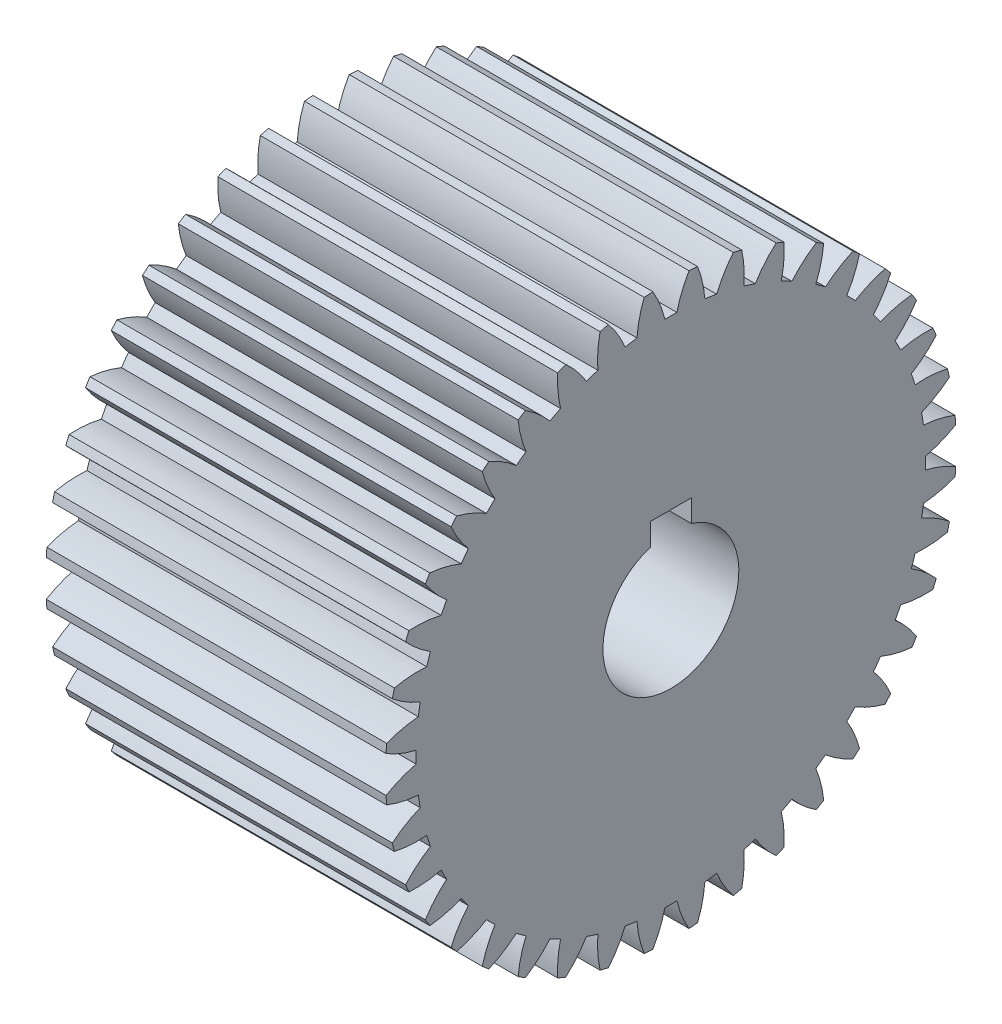
SolidWorks part; units mm, degrees
ref_plane "Plane1" through (0, 0, 0) normal (0, 0, 1) x (1, 0, 0)
ref_plane "Plane2" through (0, 0, 0) normal (0, 1, 0) x (1, 0, 0)
ref_plane "Plane3" through (0, 0, 0) normal (1, 0, 0) x (0, 0, -1)
sketch "HoldingSke" plane through (0, 0, 0) normal (0, 1, 0) x (1, 0, 0)
  line L0 (0, 0) -> (0.383, -0.3214)
  line L1 (-15, 0) -> (100, 0) construction
  line L2 (0, 0) -> (-2.1039, 2.3779)
  line L3 (0, 0) -> (-11.863, 4.5341)
  line L4 (0, 0) -> (6.6156, 5.5511)
  line L5 (0, 0) -> (-46.8476, -17.4728)
  line L6 (0, 0) -> (-41.4481, -27.9652)
  line L7 (-2.1039, 2.3779) -> (8.6586, 51.2059)
  line L8 (-76.2, 54.61) -> (-73.4, 54.61)
  line L9 (-71.009, 38.7566) -> (-53.1078, 45.2721)
  line L10 (-76.2, 71.12) -> (104.1128, 71.12)
  line L11 (0, 0) -> (-50, 0)
  line L12 (-76.2, 101.6) -> (-76.133, 101.6)
  line L13 (24.9733, 27.94) -> (52.9518, 28.4284)
  line L14 (24.9733, 27.94) -> (24.9743, 27.94)
  line L15 (24.9733, 27.94) -> (100.4006, 29.5858)
  line L16 (-63.627, -2) -> (-12.827, -2)
  circle A0 centre (0, 0) radius 10
  circle A1 centre (0, 0) radius 37.499
  circle A2 centre (0, 0) radius 37.5
  circle A3 centre (0, 0) radius 10
  dimension "Num_teeth" = 40
  dimension "Pitch_radius" = 180.3128
  dimension "Width" = 50
  dimension "Thickness" = 50
sketch "BasProSke" plane through (0, 0, 0) normal (0, 1, 0) x (1, 0, 0)
  line L0 (-10, 0) -> (60, 0) construction
  line L1 (0, 0) -> (0, 42)
  line L2 (0, 0) -> (50, 0)
  line L3 (50, 0) -> (50, 42)
  line L4 (50, 42) -> (0, 42)
  dimension "Thickness" = 50
  dimension "Diameter" = 84
revolve "Base-Revolve" add sketch "BasProSke" angle 360 about L0
sketch "TooCutSke" plane through (0, 0, 0) normal (1, 0, 0) x (0, 0, -1)
  line L1 (0, 0) -> (0, 107) construction
  line L2 (0, 0) -> (-1.6876, 39.9644) construction
  line L3 (0, 0) -> (-6.2726, 79.7007) construction
  line L4 (-1.6876, 39.9644) -> (-3.1363, 39.8504) construction
  arc A0 (0.8828, 37.4886) -> (-0.8828, 37.4886) centre (0, 0) ccw
  arc A1 (2.6784, 41.94) -> (-2.6784, 41.94) centre (0, 0) ccw
  circle A2 centre (0, 0) radius 40 construction
  circle A3 centre (0, 0) radius 37.5877 construction
  arc A4 (-0.8828, 37.4886) -> (-2.6784, 41.94) centre (-16.451, 33.7965) ccw
  arc A5 (2.6784, 41.94) -> (0.8828, 37.4886) centre (16.451, 33.7965) ccw
extrude "ToothCut" cut sketch "TooCutSke" along normal through all
fillet "Breaks" [suppressed] radius 0.04 tangent propagation no
fillet "RootFillets" [suppressed] radius 0.501
pattern_circular "TeethCuts" count 40 every 9 about axis through (-10, 0, 0) along (1, 0, 0) of "ToothCut", "RootFillets", "Breaks"
sketch "HubNeaOneSke" plane through (0, 0, 0) normal (-1, 0, 0) x (0, 0, 1)
  circle A0 centre (0, 0) radius 37.499
  dimension "Diameter" = 74.998
extrude "HubNearOne" [suppressed] add sketch "HubNeaOneSke" along normal blind 34.0001
sketch "HubNeaBotSke" plane through (0, 0, 0) normal (-1, 0, 0) x (0, 0, 1)
  circle A0 centre (0, 0) radius 37.499
  dimension "Diameter" = 74.998
extrude "HubNearBoth" [suppressed] add sketch "HubNeaBotSke" along normal blind 17
ref_plane "FarPln" through (50, 0, 0) normal (1, 0, 0) x (0, 0, -1)
sketch "HubFarSke" plane through (50, 0, 0) normal (1, 0, 0) x (0, 0, -1)
  circle A0 centre (0, 0) radius 37.499
  dimension "Diameter" = 74.998
extrude "HubFar" [suppressed] add sketch "HubFarSke" along normal blind 17
sketch "BorSke" plane through (0, 0, 0) normal (1, 0, 0) x (0, 0, -1)
  circle A0 centre (0, 0) radius 10
  dimension "Diameter" = 20
extrude "Bore" cut sketch "BorSke" along normal mid plane 100.0001
sketch "KeySke" plane through (0, 0, 0) normal (1, 0, 0) x (0, 0, -1)
  line L0 (-3, 0) -> (-3, 12.8)
  line L1 (-3, 12.8) -> (3, 12.8)
  line L2 (3, 12.8) -> (3, 0)
  line L3 (0, 0) -> (0, 34) construction
  line L4 (-3, 0) -> (3, 0)
  dimension "Width" = 6
extrude "Keyway" cut sketch "KeySke" along normal mid plane 100.0001
pattern_circular "Keyway2" [suppressed] count 2 every 90 about axis through (-10, 0, 0) along (1, 0, 0) reverse direction yes
equation "' \"Module@HoldingSke\" = 6.35"
equation "' \"Num_teeth@HoldingSke\" = 12"
equation "' \"Ap@HoldingSke\" =  20"
equation "' \"Ap@HoldingSke\" = 20"
equation "' \"Width@HoldingSke\" = 0.5 * 25.4"
equation "' \"Hub_dia@HoldingSke\"= 1 * 25.4"
equation "' \"Hub_dia@HoldingSke\" = 1 * 25.4"
equation "' \"Overall_len@HoldingSke\" = 1.0 * 25.4"
equation "' \"Bore@HoldingSke\" = 0.75 * 25.4"
equation "' \"T_dim@HoldingSke\" = 0.1 * 25.4"
equation "' \"Width@KeySke\" = 0.25 * 25.4"
equation "' \"Show_teeth@HoldingSke\" = 13"
equation "' \"Backlash@HoldingSke\" = 0.009 * 25.4"
equation "' \"Addendum_fac@HoldingSke\" = 1.0"
equation "' \"Dedendum_fac@HoldingSke\" = 1.25"
equation "' \"Dedendum_add@HoldingSke\" = 0.00005 * 25.4"
equation "' \"Clearance_fac@HoldingSke\" = 0.25"
equation "\"Pitch@HoldingSke\" = 1 / \"Module@HoldingSke\""
equation "\"Overcut_dia@TooCutSke\" = (\"Num_teeth@HoldingSke\" + 2 * \"Addendum_fac@HoldingSke\") / \"Pitch@HoldingSke\" + 0.002 * 25.4"
equation "\"Pitch_dia@TooCutSke\" = \"Num_teeth@HoldingSke\" / \"Pitch@HoldingSke\""
equation "\"Base_dia@TooCutSke\" = \"Num_teeth@HoldingSke\" / \"Pitch@HoldingSke\" * cos((\"Ap@HoldingSke\"  * 3.14159265 / 180))"
equation "\"Root_dia@TooCutSke\" = (\"Num_teeth@HoldingSke\" + 2) / \"Pitch@HoldingSke\" - 2 * (\"Addendum_fac@HoldingSke\" + \"Dedendum_fac@HoldingSke\") / \"Pitch@HoldingSke\" - \"Dedendum_add@HoldingSke\" * 2"
equation "\"Half_ang@TooCutSke\" = 180 / \"Num_teeth@HoldingSke\""
equation "\"Half_CT@TooCutSke\" = \"Num_teeth@HoldingSke\" / \"Pitch@HoldingSke\" * sin((3.14159265 / 2 / \"Num_teeth@HoldingSke\")) / 2 - 7 * \"Backlash@HoldingSke\" / 4"
equation "\"Flank_rad@TooCutSke\" = \"Num_teeth@HoldingSke\" / \"Pitch@HoldingSke\" / 5"
equation "\"Radius@RootFillets\" = \"Clearance_fac@HoldingSke\" / \"Pitch@HoldingSke\" + \"Dedendum_add@HoldingSke\""
equation "\"Break_rad@Breaks\" = 0.02 / \"Pitch@HoldingSke\""
equation "\"Thickness@HoldingSke\" = \"Width@HoldingSke\""
equation "\"OAL@HoldingSke\" = \"Thickness@HoldingSke\""
equation "\"MHD@HoldingSke\" = (\"Num_teeth@HoldingSke\" + 2) / \"Pitch@HoldingSke\" - 2 * (\"Addendum_fac@HoldingSke\" + \"Dedendum_fac@HoldingSke\")  / \"Pitch@HoldingSke\" - \"Dedendum_add@HoldingSke\" * 2"
equation "\"MBD@HoldingSke\" = (\"Num_teeth@HoldingSke\" + 2) / \"Pitch@HoldingSke\" - 2 * (\"Addendum_fac@HoldingSke\" + \"Dedendum_fac@HoldingSke\")  / \"Pitch@HoldingSke\" - \"Dedendum_add@HoldingSke\" * 2 - 0.002 * 25.4"
equation "\"MHD@HoldingSke\" = ((sgn( \"MHD@HoldingSke\" - \"Hub_dia@HoldingSke\" )-1)*( \"MHD@HoldingSke\" - \"Hub_dia@HoldingSke\" ))/-2+ \"Hub_dia@HoldingSke\""
equation "\"MBD@HoldingSke\" = ((sgn( \"MBD@HoldingSke\" - \"Bore@HoldingSke\" )-1)*( \"MBD@HoldingSke\" - \"Bore@HoldingSke\" ))/-2+ \"Bore@HoldingSke\""
equation "\"OAL@HoldingSke\" = ((sgn( \"OAL@HoldingSke\" - \"Overall_len@HoldingSke\" )+1)*( \"OAL@HoldingSke\" - \"Overall_len@HoldingSke\" ))/2 + \"Overall_len@HoldingSke\" + 0.000002 * 25.4"
equation "\"Num_teeth@TeethCuts\" = int( \"Show_teeth@HoldingSke\" ) + 1"
equation "\"Num_teeth@TeethCuts\" = ((sgn( \"Num_teeth@TeethCuts\" - \"Num_teeth@HoldingSke\" )-1)*( \"Num_teeth@TeethCuts\" - \"Num_teeth@HoldingSke\" ))/-2+ \"Num_teeth@HoldingSke\""
equation "\"Num_teeth@TeethCuts\" = ((sgn( \"Num_teeth@TeethCuts\" - 2.0)+1)*( \"Num_teeth@TeethCuts\" - 2.0))/2 +2.0"
equation "\"Angle@TeethCuts\" = 360.0 / \"Num_teeth@HoldingSke\""
equation "\"Diameter@BasProSke\" = (\"Num_teeth@HoldingSke\" + 2 * \"Addendum_fac@HoldingSke\") / \"Pitch@HoldingSke\""
equation "\"Thickness@BasProSke\"  = \"Thickness@HoldingSke\""
equation "' \"Fillet_rad@BasProSke\" =  \"Thickness@HoldingSke\" * 0.05"
equation "' \"Fillet_rad@BasProSke\" = \"Thickness@HoldingSke\" * 0.05"
equation "\"MHD@HoldingSke\" = ((sgn( \"MHD@HoldingSke\" - \"Root_dia@TooCutSke\" )-1)*( \"MHD@HoldingSke\" - \"Root_dia@TooCutSke\" ))/-2+ \"Root_dia@TooCutSke\""
equation "\"Diameter@HubNeaOneSke\" = \"MHD@HoldingSke\""
equation "\"Length@HubNearOne\" = \"OAL@HoldingSke\" - \"Thickness@BasProSke\""
equation "\"Diameter@HubNeaBotSke\" = \"MHD@HoldingSke\""
equation "\"Length@HubNearBoth\" = ( \"OAL@HoldingSke\" - \"Thickness@BasProSke\" ) / 2.0"
equation "\"Thickness@FarPln\" = \"Thickness@BasProSke\""
equation "\"Diameter@HubFarSke\" = \"MHD@HoldingSke\""
equation "\"Length@HubFar\" = ( \"OAL@HoldingSke\" - \"Thickness@BasProSke\" ) / 2.0"
equation "\"Diameter@BorSke\" = \"MBD@HoldingSke\""
equation "\"D1@Bore\" = \"OAL@HoldingSke\" * 2.0"
equation "\"D1@Keyway\" = \"OAL@HoldingSke\" * 2.0"
equation "\"Offset@KeySke\" = \"T_dim@HoldingSke\" + \"MBD@HoldingSke\" / 2.0"
